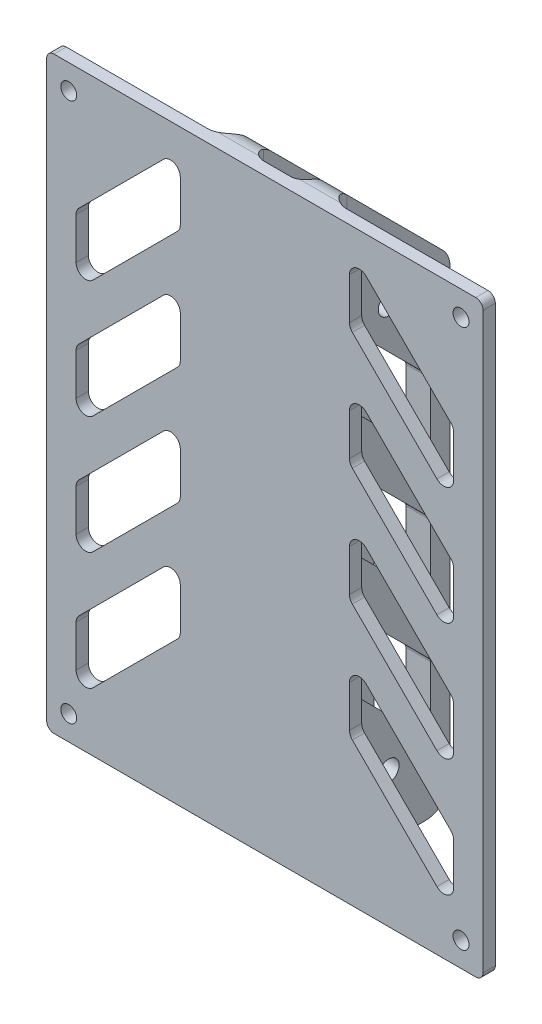
SolidWorks part; units mm, degrees
ref_plane "Front Plane" through (0, 0, 0) normal (0, 0, 1) x (1, 0, 0)
ref_plane "Top Plane" through (0, 0, 0) normal (0, 1, 0) x (1, 0, 0)
ref_plane "Right Plane" through (0, 0, 0) normal (1, 0, 0) x (0, 0, -1)
sketch "Sketch1" plane through (0, 0, 0) normal (0, 0, 1) x (1, 0, 0)
  line L1 (-89, 240) -> (89, 240)
  line L2 (-89, 240) -> (-89, 0)
  line L3 (-89, 0) -> (89, 0)
  line L4 (89, 240) -> (89, 0)
  point P4 (0, 0)
  dimension "D1" = 178
  dimension "D2" = 240
extrude "Boss-Extrude1" add sketch "Sketch1" along normal blind 5
ref_plane "Plane1" through (10.5, 0, 0) normal (1, 0, 0) x (0, 0, -1)
sketch "Sketch2" plane through (10.5, 0, 0) normal (1, 0, 0) x (0, 0, -1)
  line L0 (0, 0) -> (40, 0)
  line L1 (50, 10) -> (50, 190.8579)
  line L2 (47.0711, 197.9289) -> (7.9289, 237.0711)
  line L3 (0.8579, 240) -> (0, 240)
  line L4 (0, 0) -> (0, 240) construction
  line L5 (25, 190) -> (0, 190) construction
  line L7 (25, 190) -> (25, 25) construction
  line L8 (0, 0) -> (0, 240)
  line L9 (-5, 240) -> (0, 240) construction
  arc A0 (40, 0) -> (50, 10) centre (40, 10) ccw
  arc A1 (50, 190.8579) -> (47.0711, 197.9289) centre (40, 190.8579) ccw
  arc A2 (7.9289, 237.0711) -> (0.8579, 240) centre (0.8579, 230) ccw
  circle A3 centre (25, 190) radius 4.25
  circle A4 centre (25, 25) radius 4.25
  point P13 (50, 0)
  point P18 (5, 240)
  point P24 (0, 0)
  dimension "D4" = 10
  dimension "D5" = 10
  dimension "D6" = 10
  dimension "D7" = 8.5
  dimension "D1" = 50
  dimension "D2" = 5
  dimension "D3" = 135
  dimension "D8" = 25
  dimension "D10" = 25
  dimension "D9" = 50
extrude "Boss-Extrude2" add sketch "Sketch2" along normal blind 10
fillet "Fillet2" radius 8 1 edges at (20.5, 120, 0)
fillet "Fillet3" radius 5 1 edges at (10.5, 120, 0)
mirror "Mirror1" about plane through (0, 0, 0) normal (1, 0, 0) of "Fillet3", "Fillet2", "Boss-Extrude2"
sketch "Sketch3" plane through (0, 0, 0) normal (0, 0, -1) x (-1, 0, 0)
  line L0 (-89, 240) -> (-28.5, 240) construction
  line L1 (-80, 230) -> (80, 230) construction
  line L2 (-80, 230) -> (-80, 10) construction
  line L3 (-80, 10) -> (80, 10) construction
  line L4 (80, 230) -> (80, 10) construction
  line L5 (-80, 230) -> (80, 10) construction
  line L6 (-80, 10) -> (80, 230) construction
  line L7 (89, 240) -> (89, 0) construction
  line L8 (89, 0) -> (28.5, 0) construction
  line L9 (-89, 0) -> (-89, 240) construction
  circle A6 centre (-80, 10) radius 3.25
  circle A8 centre (80, 10) radius 3.25
  circle A9 centre (80, 230) radius 3.25
  circle A10 centre (-80, 230) radius 3.25
  point P6 (0, 120)
  dimension "D1" = 10
  dimension "D2" = 9
  dimension "D5" = 6.5
  dimension "D3" = 10
  dimension "D4" = 9
extrude "Cut-Extrude1" cut sketch "Sketch3" against normal through all
fillet "Fillet4" radius 3 4 edges at (89, 240, 2.5) (-89, 240, 2.5) (-89, 0, 2.5) (89, 0, 2.5)
sketch "Sketch4" plane through (-20.5, 0, 0) normal (-1, 0, 0) x (0, 0, 1)
  line L0 (-41.4142, 156.6152) -> (-14.4142, 183.6152)
  line L1 (-11, 182.201) -> (-11, 159.5736)
  line L2 (-11.5858, 158.1594) -> (-38.5858, 131.1594)
  line L3 (-42, 132.5736) -> (-42, 155.201)
  line L4 (-47.0711, 197.9289) -> (-8, 237) construction
  line L5 (-50, 10) -> (-50, 190.8579) construction
  line L6 (-8, 0) -> (-8, 237) construction
  line L7 (-25, 190) -> (-50, 165) construction
  line L8 (-42, 82.5736) -> (-42, 105.201)
  line L9 (-41.4142, 106.6152) -> (-14.4142, 133.6152)
  line L10 (-11, 132.201) -> (-11, 109.5736)
  line L11 (-11.5858, 108.1594) -> (-38.5858, 81.1594)
  line L12 (-42, 32.5736) -> (-42, 55.201)
  line L13 (-41.4142, 56.6152) -> (-14.4142, 83.6152)
  line L14 (-11, 82.201) -> (-11, 59.5736)
  line L15 (-11.5858, 58.1594) -> (-38.5858, 31.1594)
  arc A0 (-41.4142, 156.6152) -> (-42, 155.201) centre (-40, 155.201) ccw
  arc A1 (-38.5858, 131.1594) -> (-42, 132.5736) centre (-40, 132.5736) cw
  arc A2 (-11, 159.5736) -> (-11.5858, 158.1594) centre (-13, 159.5736) cw
  arc A3 (-14.4142, 183.6152) -> (-11, 182.201) centre (-13, 182.201) cw
  arc A4 (-38.5858, 81.1594) -> (-42, 82.5736) centre (-40, 82.5736) cw
  arc A5 (-41.4142, 106.6152) -> (-42, 105.201) centre (-40, 105.201) ccw
  arc A6 (-14.4142, 133.6152) -> (-11, 132.201) centre (-13, 132.201) cw
  arc A7 (-11, 109.5736) -> (-11.5858, 108.1594) centre (-13, 109.5736) cw
  arc A8 (-38.5858, 31.1594) -> (-42, 32.5736) centre (-40, 32.5736) cw
  arc A9 (-41.4142, 56.6152) -> (-42, 55.201) centre (-40, 55.201) ccw
  arc A10 (-14.4142, 83.6152) -> (-11, 82.201) centre (-13, 82.201) cw
  arc A11 (-11, 59.5736) -> (-11.5858, 58.1594) centre (-13, 59.5736) cw
  dimension "D5" = 2
  dimension "D1" = 3
  dimension "D2" = 8
  dimension "D3" = 12
  dimension "D4" = 20
  dimension "D6" = 3
extrude "Cut-Extrude2" cut sketch "Sketch4" against normal through all both
sketch "Sketch5" plane through (0, 0, 0) normal (0, 0, -1) x (-1, 0, 0)
  line L0 (-75.8284, 190.6716) -> (-41.3284, 225.1716)
  line L1 (-77, 187.8431) -> (-77, 170.8726)
  line L2 (-70.1716, 168.0442) -> (-35.6716, 202.5442)
  line L3 (-34.5, 205.3726) -> (-34.5, 222.3431)
  line L4 (-89, 3) -> (-89, 237) construction
  line L5 (-86, 240) -> (-28.5, 240) construction
  line L6 (-28.5, 0) -> (-28.5, 240) construction
  line L7 (-75.8284, 142.6716) -> (-41.3284, 177.1716)
  line L8 (-34.5, 157.3726) -> (-34.5, 174.3431)
  line L9 (-70.1716, 120.0442) -> (-35.6716, 154.5442)
  line L10 (-77, 139.8431) -> (-77, 122.8726)
  line L11 (-75.8284, 94.6716) -> (-41.3284, 129.1716)
  line L12 (-34.5, 109.3726) -> (-34.5, 126.3431)
  line L13 (-70.1716, 72.0442) -> (-35.6716, 106.5442)
  line L14 (-77, 91.8431) -> (-77, 74.8726)
  line L15 (-75.8284, 46.6716) -> (-41.3284, 81.1716)
  line L16 (-34.5, 61.3726) -> (-34.5, 78.3431)
  line L17 (-70.1716, 24.0442) -> (-35.6716, 58.5442)
  line L18 (-77, 43.8431) -> (-77, 26.8726)
  line L19 (0, 240) -> (0, 0) construction
  line L21 (77, 43.8431) -> (77, 26.8726)
  line L22 (70.1716, 24.0442) -> (35.6716, 58.5442)
  line L23 (34.5, 61.3726) -> (34.5, 78.3431)
  line L24 (75.8284, 46.6716) -> (41.3284, 81.1716)
  line L25 (77, 91.8431) -> (77, 74.8726)
  line L26 (70.1716, 72.0442) -> (35.6716, 106.5442)
  line L27 (34.5, 109.3726) -> (34.5, 126.3431)
  line L28 (75.8284, 94.6716) -> (41.3284, 129.1716)
  line L29 (77, 139.8431) -> (77, 122.8726)
  line L30 (70.1716, 120.0442) -> (35.6716, 154.5442)
  line L31 (34.5, 157.3726) -> (34.5, 174.3431)
  line L32 (75.8284, 142.6716) -> (41.3284, 177.1716)
  line L33 (77, 187.8431) -> (77, 170.8726)
  line L34 (70.1716, 168.0442) -> (35.6716, 202.5442)
  line L35 (34.5, 205.3726) -> (34.5, 222.3431)
  line L36 (75.8284, 190.6716) -> (41.3284, 225.1716)
  arc A0 (-35.6716, 202.5442) -> (-34.5, 205.3726) centre (-38.5, 205.3726) ccw
  arc A1 (-41.3284, 225.1716) -> (-34.5, 222.3431) centre (-38.5, 222.3431) cw
  arc A2 (-75.8284, 190.6716) -> (-77, 187.8431) centre (-73, 187.8431) ccw
  arc A3 (-77, 170.8726) -> (-70.1716, 168.0442) centre (-73, 170.8726) ccw
  arc A4 (-75.8284, 142.6716) -> (-77, 139.8431) centre (-73, 139.8431) ccw
  arc A5 (-41.3284, 177.1716) -> (-34.5, 174.3431) centre (-38.5, 174.3431) cw
  arc A6 (-35.6716, 154.5442) -> (-34.5, 157.3726) centre (-38.5, 157.3726) ccw
  arc A7 (-77, 122.8726) -> (-70.1716, 120.0442) centre (-73, 122.8726) ccw
  arc A8 (-75.8284, 94.6716) -> (-77, 91.8431) centre (-73, 91.8431) ccw
  arc A9 (-41.3284, 129.1716) -> (-34.5, 126.3431) centre (-38.5, 126.3431) cw
  arc A10 (-35.6716, 106.5442) -> (-34.5, 109.3726) centre (-38.5, 109.3726) ccw
  arc A11 (-77, 74.8726) -> (-70.1716, 72.0442) centre (-73, 74.8726) ccw
  arc A12 (-75.8284, 46.6716) -> (-77, 43.8431) centre (-73, 43.8431) ccw
  arc A13 (-41.3284, 81.1716) -> (-34.5, 78.3431) centre (-38.5, 78.3431) cw
  arc A14 (-35.6716, 58.5442) -> (-34.5, 61.3726) centre (-38.5, 61.3726) ccw
  arc A15 (-77, 26.8726) -> (-70.1716, 24.0442) centre (-73, 26.8726) ccw
  arc A16 (75.8284, 46.6716) -> (77, 43.8431) centre (73, 43.8431) cw
  arc A17 (77, 26.8726) -> (70.1716, 24.0442) centre (73, 26.8726) cw
  arc A18 (35.6716, 58.5442) -> (34.5, 61.3726) centre (38.5, 61.3726) cw
  arc A19 (41.3284, 81.1716) -> (34.5, 78.3431) centre (38.5, 78.3431) ccw
  arc A20 (75.8284, 94.6716) -> (77, 91.8431) centre (73, 91.8431) cw
  arc A21 (77, 74.8726) -> (70.1716, 72.0442) centre (73, 74.8726) cw
  arc A22 (35.6716, 106.5442) -> (34.5, 109.3726) centre (38.5, 109.3726) cw
  arc A23 (41.3284, 129.1716) -> (34.5, 126.3431) centre (38.5, 126.3431) ccw
  arc A24 (75.8284, 142.6716) -> (77, 139.8431) centre (73, 139.8431) cw
  arc A25 (77, 122.8726) -> (70.1716, 120.0442) centre (73, 122.8726) cw
  arc A26 (35.6716, 154.5442) -> (34.5, 157.3726) centre (38.5, 157.3726) cw
  arc A27 (41.3284, 177.1716) -> (34.5, 174.3431) centre (38.5, 174.3431) ccw
  arc A28 (77, 170.8726) -> (70.1716, 168.0442) centre (73, 170.8726) cw
  arc A29 (35.6716, 202.5442) -> (34.5, 205.3726) centre (38.5, 205.3726) cw
  arc A30 (41.3284, 225.1716) -> (34.5, 222.3431) centre (38.5, 222.3431) ccw
  arc A31 (75.8284, 190.6716) -> (77, 187.8431) centre (73, 187.8431) cw
  point P15 (-34.5, 232)
  dimension "D6" = 4
  dimension "D1" = 12
  dimension "D2" = 8
  dimension "D3" = 6
  dimension "D4" = 45
  dimension "D5" = 20
  dimension "D7" = 4
extrude "Cut-Extrude3" cut sketch "Sketch5" against normal through all both
sketch "Sketch7" plane through (20.5, 0, 0) normal (1, 0, 0) x (0, 0, -1)
  circle A0 centre (25, 25) radius 10
  circle A1 centre (25, 190) radius 10
  dimension "D1" = 20
  dimension "D2" = 20
ref_plane "Plane2" through (0, 5, 0) normal (0, -1, 0) x (-1, 0, 0)
sketch "Sketch8" plane through (0, 5, 0) normal (0, -1, 0) x (-1, 0, 0)
  line L0 (-20.5, 25) -> (-45.5, 0) construction
  line L1 (-20.5, 35) -> (-20.5, 15) construction
  line L2 (-28.5, 0) -> (-86, 0) construction
  line L3 (-48.3284, 0) -> (-20.5, 27.8284)
  line L4 (-20.5, 8) -> (-20.5, 27.8284)
  line L5 (-48.3284, 0) -> (-28.5, 0)
  arc A0 (-28.5, 0) -> (-20.5, 8) centre (-28.5, 8) ccw construction
  arc A1 (-28.5, 0) -> (-20.5, 8) centre (-28.5, 8) ccw
  dimension "D1" = 45
  dimension "D2" = 2
extrude "Boss-Extrude3" add sketch "Sketch8" against normal blind 6
mirror "Mirror3" about plane through (0, 0, 0) normal (1, 0, 0) of "Boss-Extrude3"
fillet "Fillet5" radius 3 16 edges at (38.4142, 11, 0) (20.5, 11, -17.9142) (20.5, 5, -17.9142) (22.8431, 5, -2.3431) (22.8431, 11, -2.3431) (38.4142, 5, 0) (-38.4142, 11, 0) (-22.8431, 11, -2.3431) (-38.4142, 5, 0) (-20.5, 5, -17.9142) (-20.5, 11, -17.9142) (-20.5, 8, -27.8284) (-48.3284, 8, 0) (-22.8431, 5, -2.3431) (20.5, 8, -27.8284) (48.3284, 8, 0)
equation "\"D8@Sketch2\"=\"D1@Sketch2\"/2"
equation "\"D10@Sketch2\"=\"D1@Sketch2\"/2"
